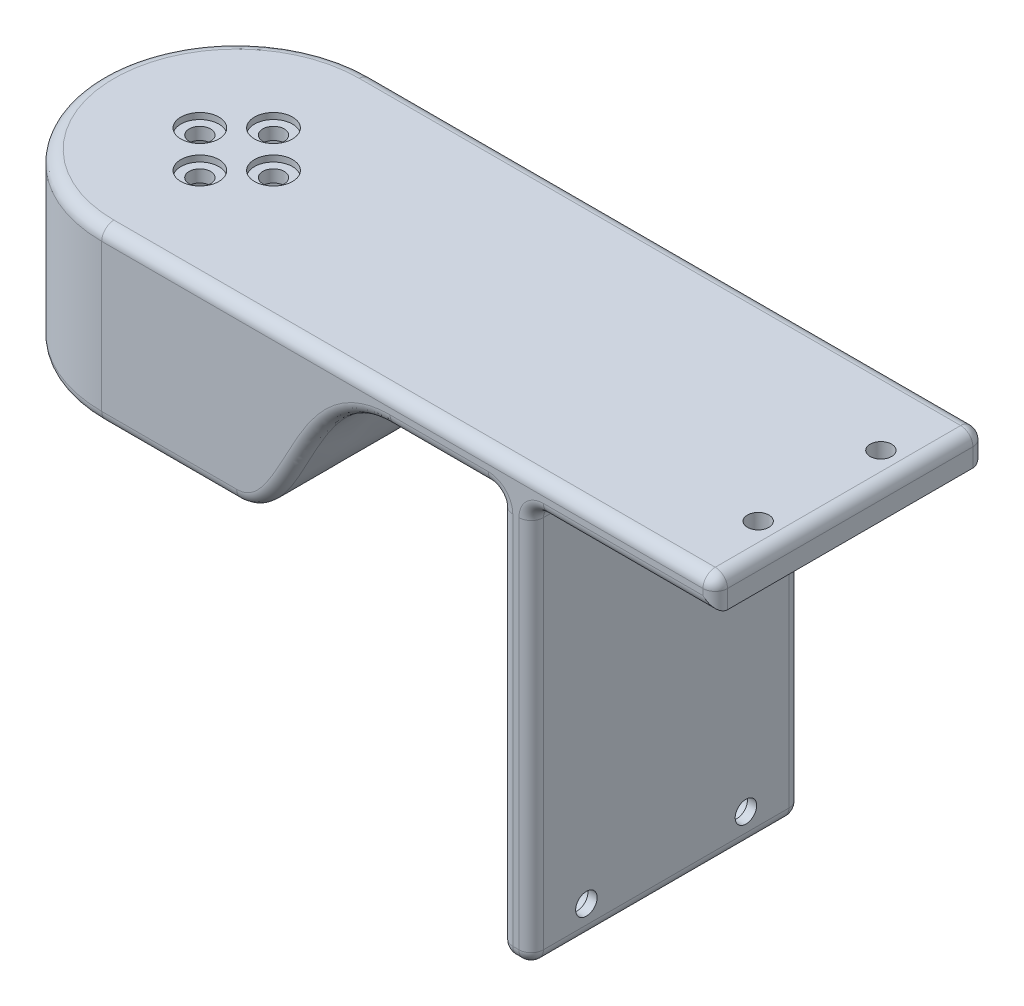
SolidWorks part; units mm, degrees
ref_plane "Front Plane" through (0, 0, 0) normal (0, 0, 1) x (1, 0, 0)
ref_plane "Top Plane" through (0, 0, 0) normal (0, 1, 0) x (1, 0, 0)
ref_plane "Right Plane" through (0, 0, 0) normal (1, 0, 0) x (0, 0, -1)
sketch "Sketch1" plane through (0, 0, 0) normal (0, 1, 0) x (1, 0, 0)
  circle A0 centre (0, 0) radius 22
  dimension "D1" = 44
extrude "Boss-Extrude1" add sketch "Sketch1" against normal blind 3
sketch "Sketch2" plane through (0, -3, 0) normal (0, -1, 0) x (1, 0, 0)
  circle A0 centre (0, 0) radius 22
  circle A1 centre (0, 0) radius 22 construction
  circle A2 centre (0, 0) radius 15.5
  dimension "D1" = 31
extrude "Boss-Extrude2" add sketch "Sketch2" along normal blind 25
sketch "Sketch3" plane through (0, 0, 0) normal (0, 1, 0) x (1, 0, 0)
  circle A0 centre (0, 0) radius 6 construction
  circle A2 centre (0, 6) radius 1.75
  circle A3 centre (0, 6) radius 3.1
  dimension "D1" = 12
  dimension "D2" = 3.5
  dimension "D3" = 6.2
extrude "Cut-Extrude1" cut sketch "Sketch3" against normal blind 1
extrude "Cut-Extrude2" cut sketch "Sketch3<2>" against normal up to next contours A2 region at (0, 0, -6)
sketch "Sketch3<2>" plane through (0, 0, 0) normal (0, 1, 0) x (1, 0, 0) same geometry as "Sketch3"
pattern_circular "CirPattern1" count 4 over 360 about axis through (0, -3, 0) along (0, 1, 0) of "Cut-Extrude1", "Cut-Extrude2"
fillet "Fillet1" radius 2 1 edges at (0, -3, -15.5)
fillet "Fillet2" radius 4 1 edges at (0, -28, -15.5)
sketch "Sketch5" plane through (0, 0, 0) normal (0, 1, 0) x (1, 0, 0)
  line L0 (0, -15.4) -> (0, 15.4) construction
  line L1 (0, 22) -> (100, 22)
  line L2 (100, 22) -> (100, -22)
  line L3 (100, -22) -> (0, -22)
  arc A0 (0, -22) -> (0, 22) centre (0, 0) ccw
  circle A1 centre (0, 0) radius 22 construction
  dimension "D1" = 100
extrude "Boss-Extrude3" add sketch "Sketch5" against normal blind 5
ref_plane "Plane1" through (22, 0, 0) normal (1, 0, 0) x (0, 0, -1)
sketch "Sketch11" plane through (22, 0, 0) normal (1, 0, 0) x (0, 0, -1)
  line L1 (-22, -28) -> (22, -28)
  line L2 (-22, -28) -> (-22, -5)
  line L3 (-22, -5) -> (22, -5)
  line L4 (22, -28) -> (22, -5)
extrude "Boss-Extrude5" add sketch "Sketch11" against normal up to surface (22 mm away) up to face at (0, -28, -22)
sketch "Sketch13" plane through (0, 0, 0) normal (0, 0, 1) x (1, 0, 0)
  line L0 (42, -1012.9226) -> (42, 48987.0774) construction
  line L5 (22, -28) -> (32, -28) construction
  line L6 (32, -28) -> (32, -5) construction
  line L7 (32, -5) -> (46.9966, -5) construction
  line L8 (22, -5) -> (100, -5) construction
  line L9 (0, -28) -> (22, -28) construction
  line L10 (22, -28) -> (22, -5)
  line L11 (22, -5) -> (46.9966, -5)
  spline S0 degree 3 poles (22, -28) (32, -28) (32, -5) (46.9966, -5) knots 0 0 0 0 1 1 1 1
  point P10 (32, -17.6615)
  point P16 (42, -6)
  dimension "D2" = 1
  dimension "D3" = 10
  dimension "D1" = 20
extrude "Boss-Extrude6" add sketch "Sketch13" against normal up to surface (22 mm away) and the other way up to surface (22 mm away) up to face at (40.6667, -11, -22) other way up to face at (40.6667, -11, 22)
sketch "Sketch15" plane through (0, -5, 0) normal (0, -1, 0) x (1, 0, 0)
  line L0 (46.9966, 22) -> (100, 22) construction
  line L1 (65, 22) -> (70, 22)
  line L2 (65, 22) -> (65, -22)
  line L3 (65, -22) -> (70, -22)
  line L4 (70, 22) -> (70, -22)
  line L5 (100, -22) -> (46.9966, -22) construction
  line L6 (0, -15.4) -> (0, 15.4) construction
  dimension "D1" = 5
  dimension "D2" = 65
extrude "Boss-Extrude7" add sketch "Sketch15" along normal blind 65
fillet "Fillet6" radius 2 25 edges at (50, 0, -22) (-22, 0, 0) (100, -2.5, 22) (85, -5, 22) (50, 0, 22) (11, -28, -22) (-22, -28, 0) (11, -28, 22) (85, -5, -22) (55.9983, -5, -22) (70, -37.5, 22) (67.5, -70, 22) (65, -37.5, 22) (55.9983, -5, 22) (65, -37.5, -22) (70, -37.5, -22) (70, -5, 0) (65, -5, 0) (100, -2.5, -22) (100, 0, 0) (67.5, -70, -22) (65, -70, 0) (70, -70, 0)
sketch "Sketch16" plane through (70, 0, 0) normal (1, 0, 0) x (0, 0, -1)
  line L0 (13, -65) -> (-13, -65) construction
  line L2 (0, 15.4) -> (0, -15.4) construction
  line L3 (20, -70) -> (-20, -70) construction
  circle A0 centre (-13, -65) radius 1.75
  circle A1 centre (13, -65) radius 1.75
  point P3 (0, -65)
  dimension "D2" = 3.5
  dimension "D3" = 3.5
  dimension "D1" = 26
  dimension "D4" = 5
extrude "Cut-Extrude4" cut sketch "Sketch16" against normal up to next
sketch "Sketch14" plane through (0, 0, 0) normal (0, 1, 0) x (1, 0, 0)
  line L0 (95, -10) -> (95, 10) construction
  line L2 (-15.4, 0) -> (15.4, 0) construction
  line L3 (100, -20) -> (100, 20) construction
  circle A0 centre (95, 10) radius 1.75
  circle A1 centre (95, -10) radius 1.75
  point P3 (95, 0)
  point P5 (0, 0)
  dimension "D1" = 3.5
  dimension "D2" = 3.5
  dimension "D3" = 20
  dimension "D4" = 5
extrude "Cut-Extrude3" cut sketch "Sketch14" against normal up to next
sketch "Sketch17" plane through (65, 0, 0) normal (-1, 0, 0) x (0, 0, 1)
  circle A0 centre (-13, -65) radius 2.2
  circle A1 centre (13, -65) radius 2.2
  dimension "D1" = 4.4
  dimension "D2" = 4.4
extrude "Cut-Extrude5" cut sketch "Sketch17" against normal blind 3.5
equation "\"D3@Sketch16\"=\"D2@Sketch16\""
equation "\"D6@Sketch10\"=\"D5@Sketch10\""
equation "\"D2@Sketch10\"=\"D1@Sketch10\""
equation "\"D4@Sketch10\"=\"D3@Sketch10\""
